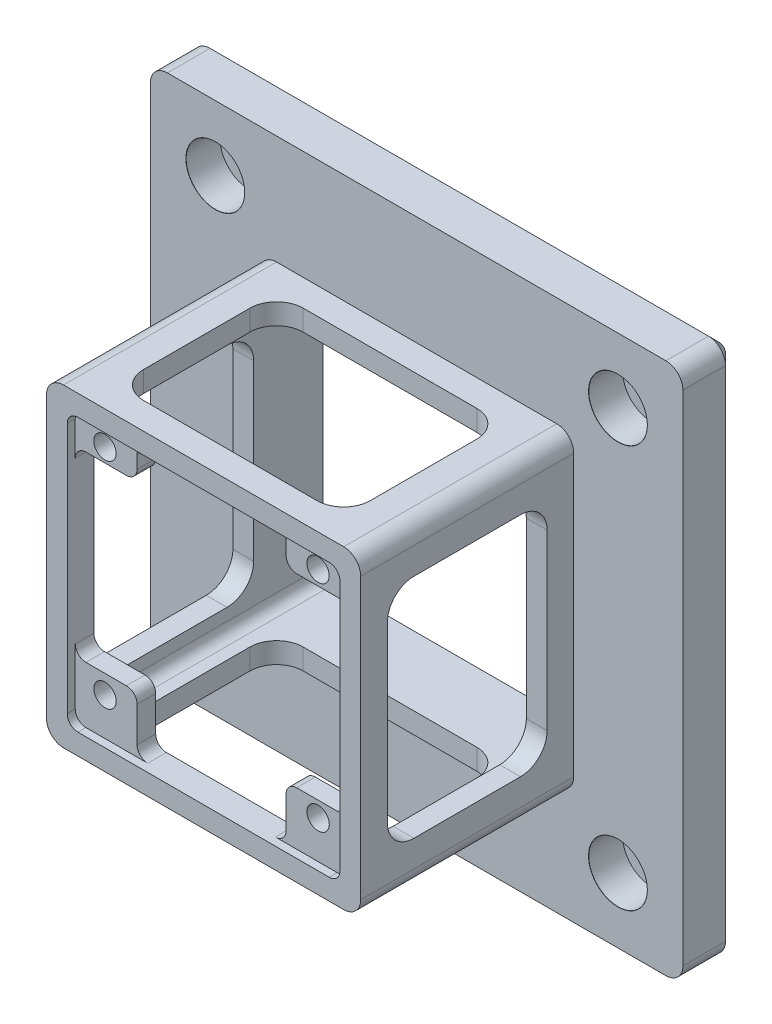
SolidWorks part; units mm, degrees
ref_plane "Front Plane" through (0, 0, 0) normal (1, 0, 0) x (0, 1, 0)
ref_plane "Top Plane" through (0, 0, 0) normal (0, 0, 1) x (0, 1, 0)
ref_plane "Right Plane" through (0, 0, 0) normal (0, 1, 0) x (-1, 0, 0)
sketch "Sketch2" plane through (0, 0, 0) normal (0, 0, 1) x (0, 1, 0)
  line L0 (25.6, 25.6) -> (50, 50)
  line L1 (-50, 50) -> (50, 50)
  line L2 (-50, 50) -> (-50, -50)
  line L3 (-50, -50) -> (50, -50)
  line L4 (50, 50) -> (50, -50)
  line L5 (-50, 50) -> (50, -50) construction
  line L6 (-50, -50) -> (50, 50) construction
  line L7 (-25.6, -25.6) -> (25.6, -25.6)
  line L8 (-25.6, -25.6) -> (-25.6, 25.6)
  line L9 (-25.6, 25.6) -> (25.6, 25.6)
  line L10 (25.6, -25.6) -> (25.6, 25.6)
  line L11 (-25.6, -25.6) -> (25.6, 25.6) construction
  line L12 (-25.6, 25.6) -> (25.6, -25.6) construction
  line L13 (25.6, -25.6) -> (50, -50)
  line L14 (37.8, 37.8) -> (37.8, -37.8)
  line L15 (37.8, -37.8) -> (37.8, -50)
  point P0 (0, 0)
  point P6 (0, 0)
  dimension "D1" = 51.2
  dimension "D2" = 100
extrude "Boss-Extrude1" add sketch "Sketch2" along normal blind 10 contours L7 L10 L9 L8 | L2 L1 L4 L3
sketch "Sketch5" plane through (0, 0, 10) normal (0, 0, 1) x (1, 0, 0)
  line L0 (-37.8, 37.8) -> (37.8, 37.8)
  line L2 (55, 0) -> (-55, 0) construction
  point P0 (-37.8, 37.8)
  point P1 (37.8, 37.8)
  point P13 (37.8, -37.8)
  point P14 (-37.8, -37.8)
hole_wizard "CBORE for M6 Hex Socket Head Cap Screw1" positions "Sketch5" profile "Sketch6" counterbore size "M6" standard "ISO" end condition through all
sketch "Sketch6" plane through (-37.8, 37.8, 10) normal (1, 0, 0) x (0, -1, 0)
  line L0 (0, 0) -> (0, 10)
  line L1 (0, 10) -> (3.3, 10)
  line L3 (3.3, 10) -> (3.3, 6.4)
  line L4 (5.5, 6.4) -> (3.3, 6.4)
  line L5 (5.5, 6.4) -> (5.5, 0.025)
  line L6 (5.5, 0.025) -> (5.525, 0)
  line L7 (5.525, 0) -> (0, 0)
  line L8 (-5.5, 0.025) -> (-5.525, 0) construction
  line L11 (0, -6.35) -> (0, 107.95) construction
  dimension "Thru Hole Dia." = 6.6
  dimension "Thru Hole Depth" = 10
  dimension "C'Bore Dia." = 11
  dimension "C'Bore Depth" = 6.4
  dimension "Near C'Sink Dia." = 11.05
  dimension "Near C'Sink Angle" = 90
sketch "Sketch7" plane through (0, 0, 10) normal (0, 0, 1) x (1, 0, 0)
  line L0 (25.6, 25.6) -> (50, 50) construction
  line L1 (-29.5, -29.5) -> (29.5, -29.5)
  line L2 (-29.5, -29.5) -> (-29.5, 29.5)
  line L3 (-29.5, 29.5) -> (29.5, 29.5)
  line L4 (29.5, -29.5) -> (29.5, 29.5)
  line L5 (-29.5, -29.5) -> (29.5, 29.5) construction
  line L6 (-29.5, 29.5) -> (29.5, -29.5) construction
  point P0 (0, 0)
  line M13 (25.6, 25.6) -> (25.6, -25.6)
  line M14 (25.6, -25.6) -> (-25.6, -25.6)
  line M15 (-25.6, -25.6) -> (-25.6, 25.6)
  line M16 (-25.6, 25.6) -> (25.6, 25.6)
  dimension "D1" = 59
extrude "Boss-Extrude2" add sketch "Sketch7" along normal blind 40 contours L1 L4 L3 L2 M16 M13 M14 M15
sketch "Sketch8" plane through (0, 0, 50) normal (0, 0, 1) x (1, 0, 0)
  line L0 (-50, -50) -> (50, 50) construction
  line L5 (-24.7015, -24.7015) -> (24.7015, 24.7015) construction
  line L6 (20, -20.6) -> (20, -25.6)
  line L7 (25.6, -25.6) -> (25.6, 25.6) construction
  line L8 (-25.6, 25.6) -> (25.6, 25.6)
  line L9 (-25.6, 25.6) -> (-25.6, 19.2)
  line L10 (-25.6, 19.2) -> (-13.9912, 19.2)
  line L11 (25.6, 25.6) -> (25.6, 19.2)
  line L13 (-25.6, 25.6) -> (-13.9912, 25.6)
  line L14 (-25.6, -25.6) -> (25.6, -25.6)
  line L15 (-25.6, -25.6) -> (-25.6, -15)
  line L17 (25.6, -25.6) -> (25.6, -15.6)
  line L18 (-19.721, 19.721) -> (24.7015, -24.7015) construction
  line L19 (13.9912, 19.2) -> (25.6, 19.2)
  line L20 (-13.9912, -25.6) -> (-13.9912, -17.5)
  line L21 (13.9912, -25.6) -> (-13.9912, -25.6)
  line L22 (13.9912, -25.6) -> (13.9912, -17.5)
  line L24 (0, -25.6) -> (0, -24.7015)
  line L27 (13.9912, 19.2) -> (13.9912, 25.6)
  line L28 (13.9912, 25.6) -> (-13.9912, 25.6)
  line L29 (-13.9912, 19.2) -> (-13.9912, 25.6)
  line L31 (-25.6, 25.6) -> (-25.6, 19.2)
  line L32 (-25.6, 19.2) -> (-13.9912, 19.2)
  line L33 (-13.9912, 25.6) -> (-13.9912, 19.2)
  line L34 (13.9912, 25.6) -> (25.6, 25.6)
  line L35 (13.9912, 25.6) -> (13.9912, 19.2)
  line L36 (13.9912, 19.2) -> (25.6, 19.2)
  line L37 (25.6, 25.6) -> (25.6, 19.2)
  line L39 (13.9912, -17.5) -> (13.9912, -25.6)
  line L40 (13.9912, -25.6) -> (25.6, -25.6)
  line L41 (25.6, -17.5) -> (25.6, -25.6)
  line L43 (-25.6, -17.5) -> (-25.6, -25.6)
  line L44 (-25.6, -25.6) -> (-13.9912, -25.6)
  line L45 (-13.9912, -17.5) -> (-13.9912, -25.6)
  line L46 (-20, -20.6) -> (-20, -25.6)
  line L47 (19.9861, 24) -> (19.9861, 25.6)
  line L48 (25.6, -15.6) -> (13.9912, -15.6)
  line L49 (25.6, -15.6) -> (25.6, -25.6)
  line L50 (25.6, -25.6) -> (13.9912, -25.6)
  line L51 (13.9912, -15.6) -> (13.9912, -25.6)
  line L52 (-25.6, -15) -> (-13.9912, -15)
  line L53 (-25.6, -15) -> (-25.6, -25.6)
  line L54 (-25.6, -25.6) -> (-13.9912, -25.6)
  line L55 (-13.9912, -15) -> (-13.9912, -25.6)
  circle A0 centre (-20.0139, 21.8005) radius 2.1
  circle A1 centre (19.9861, 21.9) radius 2.1
  circle A2 centre (20, -18.5) radius 2.1
  circle A3 centre (-20, -18.5) radius 2.1
  point P0 (0, 0)
  dimension "D5" = 4.2
  dimension "D6" = 5
  dimension "D8" = 4.2
  dimension "D10" = 4.2
  dimension "D1" = 49.403
  dimension "D2" = 6.4
  dimension "D3" = 10
  dimension "D4" = 40
  dimension "D7" = 40
  dimension "D9" = 5
  dimension "D11" = 1.6
other "AlignGroup1"
extrude "Boss-Extrude3" add sketch "Sketch8" against normal blind 5
fillet "Fillet1" radius 3.2 8 edges at (-29.5, -29.5, 30) (-50, -50, 5) (29.5, -29.5, 30) (50, -50, 5) (50, 50, 5) (29.5, 29.5, 30) (-50, 50, 5) (-29.5, 29.5, 30)
sketch "Sketch11" plane through (-29.5, 0, 0) normal (-1, 0, 0) x (0, -1, 0)
  line L1 (-21.3, 15) -> (21.3, 15)
  line L2 (21.3, 15) -> (21.3, 45)
  line L3 (21.3, 45) -> (-21.3, 45)
  line L4 (-21.3, 45) -> (-21.3, 15)
  line L5 (-26.3, 10) -> (26.3, 10)
  line L6 (26.3, 10) -> (26.3, 50)
  line L7 (26.3, 50) -> (-26.3, 50)
  line L8 (-26.3, 50) -> (-26.3, 10)
  line L9 (-26.3, 10) -> (26.3, 10)
  line L10 (26.3, 10) -> (26.3, 50)
  line L11 (26.3, 50) -> (-26.3, 50)
  line L12 (-26.3, 50) -> (-26.3, 10)
  line L13 (-26.3, 15) -> (26.3, 15)
  dimension "D3" = 5
  dimension "D1" = 0
  dimension "D2" = 5
extrude "Cut-Extrude2" cut sketch "Sketch11" against normal through all contours L3 L4 L1 L2
sketch "Sketch12" plane through (0, -29.5, 0) normal (0, -1, 0) x (1, 0, 0)
  line L0 (21.3, 45) -> (-21.3, 45)
  line L1 (-21.3, 45) -> (-21.3, 15)
  line L2 (-21.3, 15) -> (21.3, 15)
  line L3 (21.3, 15) -> (21.3, 45)
  line L4 (26.3, 50) -> (-26.3, 50)
  line L5 (-26.3, 50) -> (-26.3, 10)
  line L6 (-26.3, 10) -> (26.3, 10)
  line L7 (26.3, 10) -> (26.3, 50)
  line L8 (26.3, 50) -> (-26.3, 50)
  line L9 (-26.3, 50) -> (-26.3, 10)
  line L10 (-26.3, 10) -> (26.3, 10)
  line L11 (26.3, 10) -> (26.3, 50)
  dimension "D1" = 0
  dimension "D2" = 5
extrude "Cut-Extrude3" cut sketch "Sketch12" against normal through all contours L0 L1 L2 L3
fillet "Fillet3" radius 5 12 edges at (-21.3, -27.55, 45) (-21.3, -27.55, 15) (-27.55, -21.3, 45) (-27.55, -21.3, 15) (-21.3, 27.55, 15) (-21.3, 27.55, 45) (21.3, 27.55, 15) (21.3, 27.55, 45) (27.55, -21.3, 45) (27.55, 21.3, 45) (27.55, 21.3, 15) (27.55, -21.3, 15)
fillet "Fillet4" radius 5 4 edges at (-27.55, 21.3, 45) (-27.55, 21.3, 15) (21.3, -27.55, 15) (21.3, -27.55, 45)
chamfer "Chamfer2" distance 2 angle 45 8 edges at (0, 50, 0) (50, 0, 0) (0, -50, 0) (49.0627, -49.0627, 0) (49.0627, 49.0627, 0) (-49.0627, -49.0627, 0) (-49.0627, 49.0627, 0) (-50, 0, 0)
chamfer "Chamfer3" distance 2 angle 45 4 edges at (25.6, 0, 0) (0, 25.6, 0) (0, -25.6, 0) (-25.6, 0, 0)
sketch "Sketch13" plane through (0, 0, 50) normal (0, 0, 1) x (1, 0, 0)
  line L6 (13.9912, 19.2) -> (13.9912, 25.5)
  line L7 (25.6, -25.6) -> (-25.6, -25.6)
  line L8 (25.6, -25.6) -> (25.6, 25.6)
  line L9 (25.6, 25.6) -> (-25.6, 25.6)
  line L10 (-25.6, -25.6) -> (-25.6, 25.6)
extrude "Cut-Extrude4" cut sketch "Sketch13" against normal blind 1.5 contours L8 L7 L10 L9
fillet "Fillet5" radius 2 20 edges at (-25.6, -25.6, 23.5) (25.6, -25.6, 23.5) (-25.6, 25.6, 23.5) (25.6, 25.6, 23.5) (-25.6, -15, 46.75) (-13.9912, -15, 46.75) (-13.9912, -25.6, 46.75) (13.9912, -25.6, 46.75) (13.9912, -15.6, 46.75) (25.6, -15.6, 46.75) (25.6, 19.2, 46.75) (13.9912, 19.2, 46.75) (13.9912, 25.6, 46.75) (-13.9912, 19.2, 46.75) (-25.6, 19.2, 46.75) (-13.9912, 25.6, 46.75) (25.6, 25.6, 49.25) (-25.6, -25.6, 49.25) (25.6, -25.6, 49.25) (-25.6, 25.6, 49.25)
